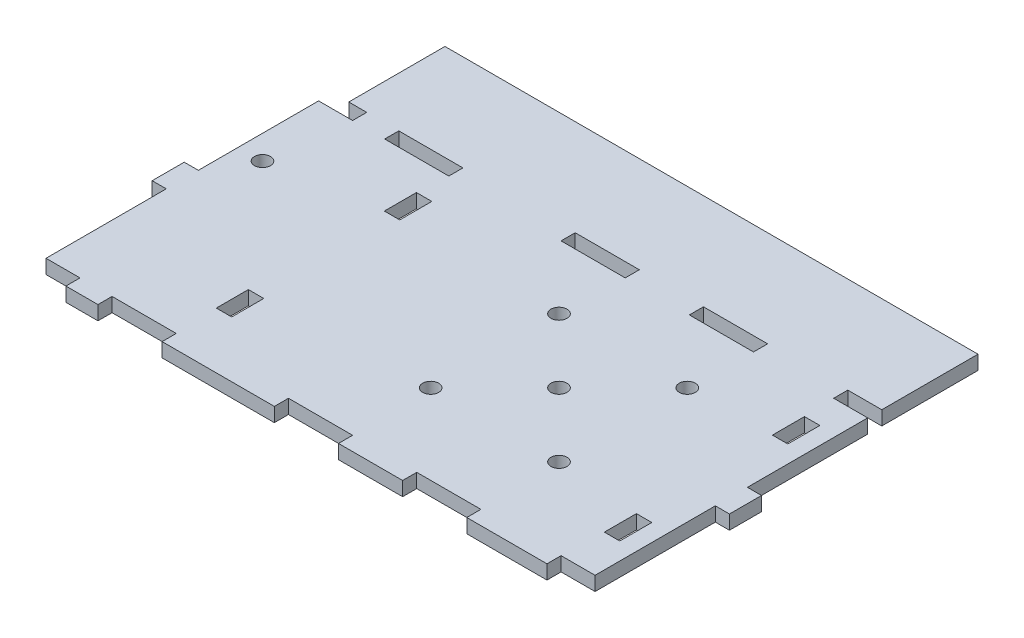
SolidWorks part; units mm, degrees
ref_plane "Front Plane" through (0, 0, 0) normal (0, 0, 1) x (1, 0, 0)
ref_plane "Top Plane" through (0, 0, 0) normal (0, 1, 0) x (1, 0, 0)
ref_plane "Right Plane" through (0, 0, 0) normal (1, 0, 0) x (0, 0, -1)
sketch "Sketch1" plane through (0, 0, 0) normal (0, 1, 0) x (1, 0, 0)
  line L0 (-108.712, 6.35) -> (-114.3, 6.35)
  line L2 (-108.712, -53.975) -> (-108.712, -6.35)
  line L4 (108.712, -53.975) -> (108.712, -6.35)
  line L5 (-108.712, -53.975) -> (108.712, 53.975) construction
  line L6 (-108.712, 53.975) -> (108.712, -53.975) construction
  line L7 (-114.3, 6.35) -> (-114.3, -6.35)
  line L8 (-114.3, -6.35) -> (-108.712, -6.35)
  line L9 (-108.712, 6.35) -> (-108.712, 53.975)
  line L10 (0, 60.325) -> (0, -60.325) construction
  line L11 (114.3, -6.35) -> (108.712, -6.35)
  line L12 (114.3, 6.35) -> (114.3, -6.35)
  line L13 (108.712, 6.35) -> (114.3, 6.35)
  line L14 (108.712, 6.35) -> (108.712, 53.975)
  line L23 (-108.712, 0) -> (106.818, 0) construction
  line L32 (-108.712, 53.975) -> (-95.25, 53.975)
  line L33 (-108.712, -53.975) -> (-95.25, -53.975)
  line L34 (-82.55, 53.975) -> (-57.15, 53.975)
  line L36 (-95.25, 53.975) -> (-95.25, 59.563)
  line L38 (-82.55, 53.975) -> (-82.55, 59.563)
  line L40 (-57.15, 53.975) -> (-57.15, 59.563)
  line L42 (-12.7, 53.975) -> (-12.7, 59.563)
  line L44 (12.7, 53.975) -> (12.7, 59.563)
  line L46 (38.1, 53.975) -> (38.1, 59.563)
  line L48 (63.5, 53.975) -> (63.5, 59.563)
  line L50 (95.25, 53.975) -> (95.25, 59.563)
  line L51 (-12.7, 53.975) -> (12.7, 53.975)
  line L52 (38.1, 53.975) -> (63.5, 53.975)
  line L53 (95.25, 53.975) -> (108.712, 53.975)
  line L54 (95.25, -53.975) -> (95.25, -59.563)
  line L55 (63.5, -59.563) -> (95.25, -59.563)
  line L56 (63.5, -53.975) -> (63.5, -59.563)
  line L57 (38.1, -53.975) -> (38.1, -59.563)
  line L58 (12.7, -59.563) -> (38.1, -59.563)
  line L59 (12.7, -53.975) -> (12.7, -59.563)
  line L60 (-12.7, -53.975) -> (-12.7, -59.563)
  line L61 (-57.15, -59.563) -> (-12.7, -59.563)
  line L62 (-57.15, -53.975) -> (-57.15, -59.563)
  line L63 (-82.55, -53.975) -> (-82.55, -59.563)
  line L64 (-95.25, -59.563) -> (-82.55, -59.563)
  line L65 (-95.25, -53.975) -> (-95.25, -59.563)
  line L66 (-82.55, -53.975) -> (-57.15, -53.975)
  line L67 (-12.7, -53.975) -> (12.7, -53.975)
  line L68 (38.1, -53.975) -> (63.5, -53.975)
  line L69 (95.25, -53.975) -> (108.712, -53.975)
  line L70 (95.25, 59.563) -> (108.712, 59.563)
  line L71 (108.712, 59.563) -> (108.712, 97.663)
  line L72 (-95.25, 59.563) -> (-102.362, 59.563)
  line L73 (-102.362, 59.563) -> (-102.362, 97.663)
  line L74 (-102.362, 97.663) -> (108.712, 97.663)
  line L75 (63.5, 59.563) -> (38.1, 59.563)
  line L76 (12.7, 59.563) -> (-12.7, 59.563)
  line L77 (-57.15, 59.563) -> (-82.55, 59.563)
  point P0 (0, 0)
  dimension "D1" = 107.95
  dimension "D2" = 217.424
  dimension "D3" = 12.7
  dimension "D4" = 5.588
  dimension "D5" = 5.588
  dimension "D6" = 12.7
  dimension "D7" = 25.4
  dimension "D8" = 13.462
  dimension "D9" = 38.1
extrude "Boss-Extrude1" add sketch "Sketch1" along normal blind 5.588
sketch "Sketch9" plane through (0, 5.588, 0) normal (0, 1, 0) x (1, 0, 0)
  line L0 (-108.712, -6.35) -> (-108.712, -53.975) construction
  line L1 (-57.912, -24.638) -> (-51.816, -24.638)
  line L2 (-57.912, -24.638) -> (-57.912, -37.338)
  line L3 (-57.912, -37.338) -> (-51.816, -37.338)
  line L4 (-51.816, -24.638) -> (-51.816, -37.338)
  line L5 (-82.55, -53.975) -> (-57.15, -53.975) construction
  line L6 (-57.912, 29.21) -> (-51.816, 29.21)
  line L7 (-57.912, 29.21) -> (-57.912, 41.91)
  line L8 (-57.912, 41.91) -> (-51.816, 41.91)
  line L9 (-51.816, 29.21) -> (-51.816, 41.91)
  line L10 (95.758, -24.638) -> (101.854, -24.638)
  line L11 (95.758, -24.638) -> (95.758, -37.338)
  line L12 (95.758, -37.338) -> (101.854, -37.338)
  line L13 (101.854, -24.638) -> (101.854, -37.338)
  line L14 (95.758, 41.91) -> (101.854, 41.91)
  line L15 (95.758, 41.91) -> (95.758, 29.21)
  line L16 (95.758, 29.21) -> (101.854, 29.21)
  line L17 (101.854, 41.91) -> (101.854, 29.21)
  line L18 (108.712, -53.975) -> (108.712, -6.35) construction
  line L19 (108.712, 6.35) -> (108.712, 53.975) construction
  point P24 (0, 0)
  dimension "D1" = 12.7
  dimension "D2" = 6.096
  dimension "D3" = 50.8
  dimension "D4" = 16.637
  dimension "D5" = 50.8
  dimension "D6" = 83.185
  dimension "D7" = 12.7
  dimension "D8" = 6.096
  dimension "D9" = 12.7
  dimension "D10" = 6.096
  dimension "D11" = 6.096
  dimension "D12" = 12.7
  dimension "D13" = 6.858
  dimension "D14" = 6.858
extrude "Cut-Extrude1" cut sketch "Sketch9" against normal up to next
sketch "Sketch12" plane through (0, 5.588, 0) normal (0, 1, 0) x (1, 0, 0)
  line L0 (-95.25, 53.975) -> (-108.712, 53.975) construction
  line L1 (-108.712, 53.975) -> (-108.712, 6.35) construction
  circle A0 centre (-99.187, 22.225) radius 3.175
  point P4 (-101.981, 53.975)
  dimension "D1" = 6.35
  dimension "D2" = 31.75
  dimension "D3" = 9.525
extrude "Cut-Extrude2" cut sketch "Sketch12" against normal up to next
sketch "Sketch13" plane through (0, 0, 0) normal (0, -1, 0) x (1, 0, 0)
  line L0 (38.1, -53.975) -> (63.5, -53.975) construction
  circle A0 centre (62.6731, 22.225) radius 3.175
  circle A1 centre (11.8731, 22.225) radius 3.175
  circle A2 centre (11.8731, -28.575) radius 3.175
  circle A3 centre (62.6731, -28.575) radius 3.175
  circle A4 centre (37.2731, -3.175) radius 3.175
  point P10 (0, 0)
  point P13 (0, 0)
  point P14 (0, 0)
  point P15 (0, 0)
  dimension "D1" = 6.35
  dimension "D2" = 50.8
  dimension "D4" = 50.8
  dimension "D5" = 50.8
  dimension "D6" = 25.4
  dimension "D7" = 25.4
  dimension "D8" = 25.4
extrude "Cut-Extrude3" cut sketch "Sketch13" against normal up to next
sketch "Sketch14" plane through (0, 5.588, 0) normal (0, 1, 0) x (1, 0, 0)
  line L0 (108.712, -53.975) -> (108.712, -6.35) construction
  line L1 (102.362, -6.35) -> (105.537, -6.35)
  line L2 (102.362, -6.35) -> (102.362, 6.35)
  line L3 (102.362, 6.35) -> (105.537, 6.35)
  line L4 (105.537, -6.35) -> (105.537, 6.35)
  line L5 (108.712, -6.35) -> (114.3, -6.35) construction
  dimension "D1" = 3.175
  dimension "D2" = 12.7
  dimension "D3" = 3.175
